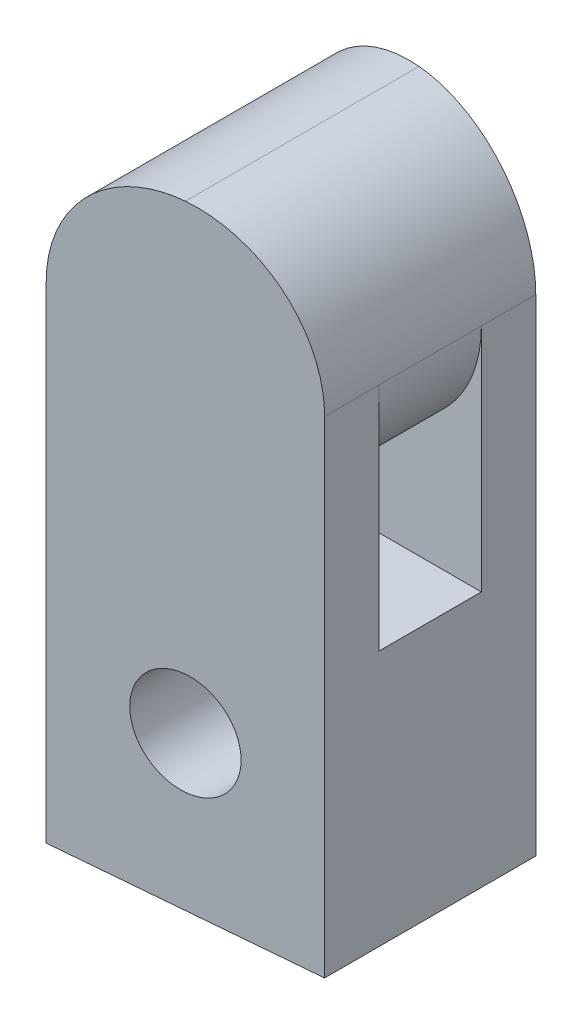
SolidWorks part; units mm, degrees
ref_plane "Front Plane" through (0, 0, 0) normal (0, 0, 1) x (1, 0, 0)
ref_plane "Top Plane" through (0, 0, 0) normal (0, 1, 0) x (1, 0, 0)
ref_plane "Right Plane" through (0, 0, 0) normal (1, 0, 0) x (0, 0, -1)
sketch "Sketch2" plane through (0, 0, 0) normal (0, 1, 0) x (1, 0, 0)
  line L0 (-2.5, -2.5) -> (2.5, -2.5) construction
  line L1 (-2.5, -2.5) -> (-2.5, 2.5)
  line L2 (2.5, -2.5) -> (2.5, 2.5) construction
  line L3 (-2.5, 2.5) -> (2.5, 2.5) construction
  line L4 (-2.5, -2.5) -> (2.5, 2.5) construction
  line L5 (2.5, -2.5) -> (-2.5, 2.5) construction
  line L6 (-2.5, 2.5) -> (2.5, 2.0626)
  line L7 (-2.5, -2.5) -> (2.5, -2.0626)
  line L8 (2.5, -2.0626) -> (2.5, 2.0626)
  point P1 (0, 0)
  dimension "D1" = 5
  dimension "D2" = 5
  dimension "D3" = 5
  dimension "D4" = 5
extrude "Boss-Extrude1" add sketch "Sketch2" along normal blind 10
sketch "Sketch3" plane through (0, 10, 0) normal (0, 1, 0) x (1, 0, 0)
  line L4 (2.5, -2.0626) -> (2.5, 2.0626)
  line L5 (2.5, 2.0626) -> (-2.5, 2.5)
  line L6 (-2.5, 2.5) -> (-2.5, -2.5)
  line L7 (-2.5, -2.5) -> (2.5, -2.0626)
  line L8 (2.5, -2.0626) -> (2.5, 2.0626)
  line L9 (2.5, 2.0626) -> (-2.5, 2.5)
  line L10 (-2.5, 2.5) -> (-2.5, -2.5)
  line L11 (-2.5, -2.5) -> (2.5, -2.0626)
  dimension "D1" = 0
extrude "Boss-Extrude2" add sketch "Sketch3" along normal blind 2
sketch "Sketch4" plane through (2.5, 0, 0) normal (1, 0, 0) x (0, 0, -1)
  line L0 (0, 0) -> (0, 12) construction
  line L1 (-2.0626, 12) -> (2.0626, 12) construction
  line L3 (-1, 5) -> (1, 5)
  line L4 (-1, 5) -> (-1, 7)
  line L5 (-1, 7) -> (1, 7)
  line L6 (1, 5) -> (1, 7)
  line L7 (-1, 5) -> (1, 7) construction
  line L8 (-1, 7) -> (1, 5) construction
  point P5 (0, 6)
  dimension "D1" = 2
  dimension "D2" = 2
extrude "Cut-Extrude1" cut sketch "Sketch4" against normal up to surface (5 mm away) up to face at (-2.5, 6, 0)
fillet "Fillet1" radius 2.5 4 edges at (2.5, 12, 0) (-2.5, 12, 0) (-2.5, 7, 0) (2.5, 7, 0)
sketch "Sketch6" plane through (0, 0, 0) normal (0, 0, 1) x (1, 0, 0)
  line L0 (0, 0) -> (0, 3) construction
  circle A0 centre (0, 3) radius 1
  dimension "D2" = 2
  dimension "D1" = 3
extrude "Cut-Extrude2" cut sketch "Sketch6" against normal through all both and the other way through all
equation "\"chuck_width\" = 5"
equation "\"D3@Sketch2\"=\"chuck_width\""
equation "\"chuck_length\" = 5"
equation "\"D4@Sketch2\"=\"chuck_length\""
equation "\"chuck_angle\"=5"
equation "\"D2@Sketch2\"=\"chuck_angle\""
equation "\"D1@Sketch2\"=\"chuck_angle\""
equation "\"chuck_depth\"=10"
equation "\"chuck_height\"= 2"
equation "\"pin_offset\"= 3"
equation "\"D1@Sketch6\"=\"pin_offset\""
equation "\"pin_dia\"=2"
equation "\"D2@Sketch6\"=\"pin_dia\""
